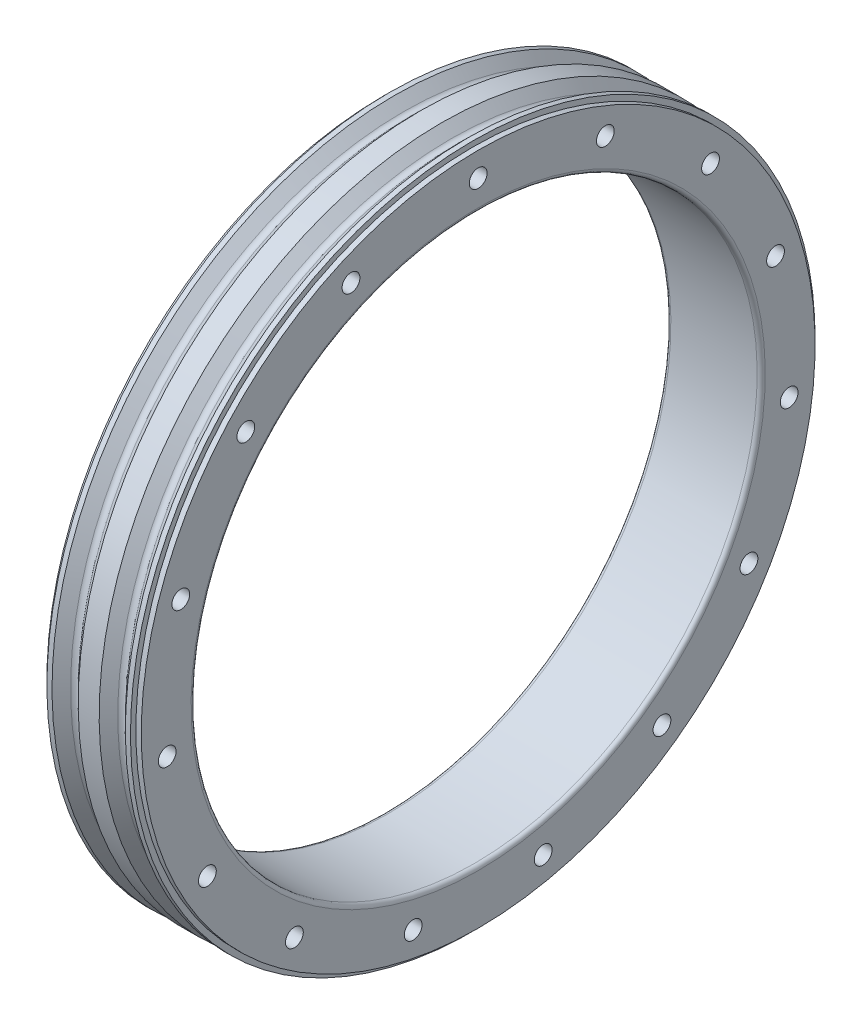
SolidWorks part; units mm, degrees
ref_plane "Front Plane" through (0, 0, 0) normal (0, 0, 1) x (1, 0, 0)
ref_plane "Top Plane" through (0, 0, 0) normal (0, 1, 0) x (1, 0, 0)
ref_plane "Right Plane" through (0, 0, 0) normal (1, 0, 0) x (0, 0, -1)
sketch "Sketch2" plane through (0, 0, 0) normal (0, 0, 1) x (1, 0, 0)
  line L0 (0, 0) -> (-72.2826, 0) construction
  line L1 (0, 116) -> (0, 0) construction
  line L2 (17.5, 127) -> (-17.5, 127)
  line L3 (17.5, 127) -> (17.5, 105)
  line L4 (17.5, 105) -> (-17.5, 105)
  line L5 (-17.5, 127) -> (-17.5, 105)
  line L6 (17.5, 127) -> (-17.5, 105) construction
  line L7 (17.5, 105) -> (-17.5, 127) construction
  line L8 (0, 116) -> (-17.5, 116) construction
  line L9 (-8.75, 116) -> (-8.75, 178.2766) construction
  line L10 (-8.75, 134.864) -> (-2.386, 128.5)
  line L11 (-8.75, 134.864) -> (-15.114, 128.5)
  line L12 (-2.386, 128.5) -> (-8.75, 122.136)
  line L13 (-15.114, 128.5) -> (-8.75, 122.136)
  line L14 (-8.75, 134.864) -> (-8.75, 122.136) construction
  line L15 (-2.386, 128.5) -> (-15.114, 128.5) construction
  line L16 (15.114, 128.5) -> (8.75, 122.136)
  line L17 (8.75, 134.864) -> (15.114, 128.5)
  line L18 (8.75, 134.864) -> (2.386, 128.5)
  line L19 (2.386, 128.5) -> (8.75, 122.136)
  point P3 (0, 116)
  point P15 (-8.75, 128.5)
  dimension "D1" = 35
  dimension "D2" = 9
  dimension "D3" = 1.5
  dimension "D4" = 105
  dimension "D5" = 128.5
revolve "Revolve1" add sketch "Sketch2" angle 360 about L0 region at (0, 115.386, 0)
ref_axis "Axis1" through (-17.5, 0, 0) along (1, 0, 0)
fillet "Fillet1" radius 2 2 edges at (8.75, 122.136, 0) (-8.75, 122.136, 0)
sketch "Sketch5" plane through (-17.5, 0, 0) normal (-1, 0, 0) x (0, 0, 1)
  line L0 (0, 127) -> (0, 105) construction
  circle A0 centre (0, 0) radius 127 construction
  circle A1 centre (0, 0) radius 105 construction
  point P7 (0, 116)
hole_wizard "CBORE for M6 Hex Head Bolt1" positions "3DSketch2" profile "Sketch6" counterbore size "M6" standard "ISO" end condition through all
sketch3d "3DSketch2"
  point P0 (-17.5, 116, 0)
sketch "Sketch6" plane through (-17.5, 116, 0) normal (0, 1, 0) x (0, 0, 1)
  line L0 (0, 0) -> (0, 35)
  line L1 (0, 35) -> (3.3, 35)
  line L3 (3.3, 35) -> (3.3, 4)
  line L4 (3.3, 4) -> (7.2735, 4)
  line L5 (7.2735, 4) -> (7.2735, 0)
  line L7 (7.2735, 0) -> (0, 0)
  line L11 (0, -6.35) -> (0, 107.95) construction
  dimension "Thru Hole Dia." = 6.6
  dimension "Thru Hole Depth" = 35
  dimension "C'Bore Dia." = 14.547
  dimension "C'Bore Depth" = 4
pattern_circular "CirPattern1" count 15 over 360 about axis through (-17.5, 0, 0) along (1, 0, 0) of "CBORE for M6 Hex Head Bolt1"
sketch "Sketch7" plane through (17.5, 0, 0) normal (1, 0, 0) x (0, 0, -1)
  circle A3 centre (0, 0) radius 127 construction
  circle A4 centre (0, 0) radius 127
  circle A5 centre (0, 0) radius 125
  dimension "D1" = 2
extrude "Cut-Extrude2" cut sketch "Sketch7" against normal blind 2
mirror "Mirror1" about plane through (0, 0, 0) normal (1, 0, 0) of "Cut-Extrude2"
fillet "Fillet2" radius 1.5 2 edges at (-17.5, 105, 0) (17.5, 105, 0)
